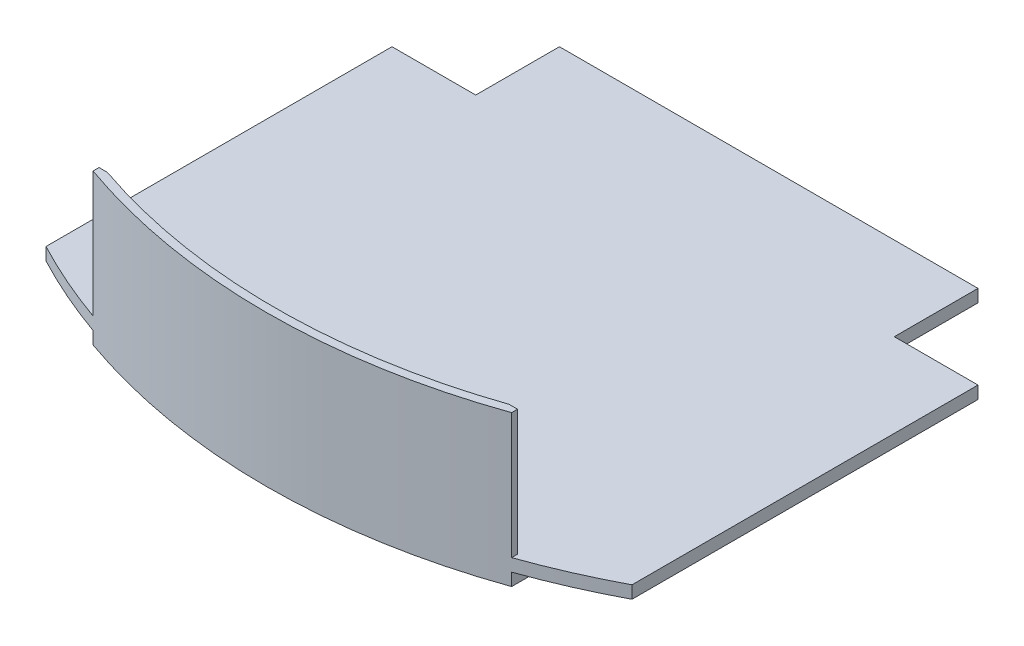
SolidWorks part; units mm, degrees
ref_plane "Front Plane" through (0, 0, 0) normal (0, 0, 1) x (1, 0, 0)
ref_plane "Top Plane" through (0, 0, 0) normal (0, 1, 0) x (1, 0, 0)
ref_plane "Right Plane" through (0, 0, 0) normal (1, 0, 0) x (0, 0, -1)
sketch "Sketch2" plane through (0, 0, 0) normal (0, 1, 0) x (1, 0, 0)
  line L3 (0, -50) -> (-70, -50)
  line L4 (-70, -50) -> (70, -50)
  line L5 (-50, -30) -> (50, -30)
  line L6 (-50, -30) -> (-50, -141.4214)
  line L7 (50, -30) -> (50, -141.4214)
  line L8 (-70, -50) -> (-70, -132.665)
  line L9 (70, -50) -> (70, -132.665)
  arc A1 (-70, -132.665) -> (70, -132.665) centre (0, 0) ccw
  point P3 (0, -50)
  point P9 (0, -30)
  point P13 (-50, 0)
  point P14 (50, 0)
  point P19 (-75, 0)
  point P20 (83.8555, 0)
  point P21 (-70, 0)
  point P22 (70, 0)
  dimension "D3" = 20
  dimension "D6" = 20
  dimension "D7" = 20
extrude "Boss-Extrude1" add sketch "Sketch2" along normal blind 6 contours L6 A1 L7 L4 L3 | L8 A1 L6 L4 | L7 A1 L9 L4 | L7 L5 L6 L3 L4 region at (0, 0, 98.6204) region at (0, 0, 40) region at (-59.8331, 0, 93.7029) region at (59.8331, 0, 93.7029)
sketch "Sketch3" plane through (0, 6, 0) normal (0, 1, 0) x (-1, 0, 0)
  line L0 (50, 50) -> (-50, 50)
  line L1 (-50, 50) -> (-50, 141.4214)
  line L2 (50, 50) -> (50, 141.4214)
  arc A0 (70, 132.665) -> (-70, 132.665) centre (0, 0) ccw construction
  arc A1 (50, 141.4214) -> (-50, 141.4214) centre (0, 0) ccw
extrude "Boss-Extrude2" add sketch "Sketch3" along normal blind 30
sketch "Sketch4" plane through (0, 0, 0) normal (0, -1, 0) x (1, 0, 0)
  line L0 (-50, 141.4214) -> (-50, 50)
  line L1 (-50, 50) -> (-70, 50)
  line L2 (-70, 50) -> (-70, 132.665)
  line L3 (-70, 50) -> (-70, 132.665) construction
  arc A0 (70, 132.665) -> (-70, 132.665) centre (0, 0) ccw construction
  arc A1 (-70, 132.665) -> (-50, 141.4214) centre (0, 0) cw
extrude "Cut-Extrude1" cut sketch "Sketch4" against normal blind 3
sketch "Sketch5" plane through (0, 0, 0) normal (0, -1, 0) x (1, 0, 0)
  line L0 (50, 141.4214) -> (50, 50)
  line L1 (50, 50) -> (70, 50)
  line L2 (70, 50) -> (70, 132.665)
  arc A0 (50, 141.4214) -> (70, 132.665) centre (0, 0) cw
extrude "Cut-Extrude2" cut sketch "Sketch5" against normal blind 3
sketch "Sketch6" plane through (0, 0, 0) normal (0, -1, 0) x (1, 0, 0)
  line L0 (-50, 50) -> (50, 50)
  line L1 (50, 50) -> (50, 30)
  line L2 (-50, 50) -> (-50, 30)
  line L3 (-50, 30) -> (50, 30)
extrude "Cut-Extrude3" cut sketch "Sketch6" against normal blind 3
shell "Shell4" thickness 2 removed face at (0, 36, 97.8553)
sketch "Sketch7" plane through (-50, 0, 0) normal (-1, 0, 0) x (0, 0, 1)
  line L0 (50, 6) -> (50, 36)
  line L1 (50, 36) -> (140, 36)
  line L2 (140, 36) -> (140, 6)
  line L3 (141.4214, 6) -> (132.665, 6) construction
  line L4 (140, 36) -> (140, 2) construction
  line L5 (140, 6) -> (50, 6)
extrude "Cut-Extrude4" cut sketch "Sketch7" against normal up to next
sketch "Sketch8" plane through (0, 0, 0) normal (0, -1, 0) x (1, 0, 0)
  line L0 (-48, 140) -> (-48, 52)
  line L1 (-48, 52) -> (48, 52)
  line L2 (48, 52) -> (48, 140)
  arc A0 (-48, 140) -> (48, 140) centre (0, 0) cw
extrude "Boss-Extrude3" add sketch "Sketch8" against normal blind 6
